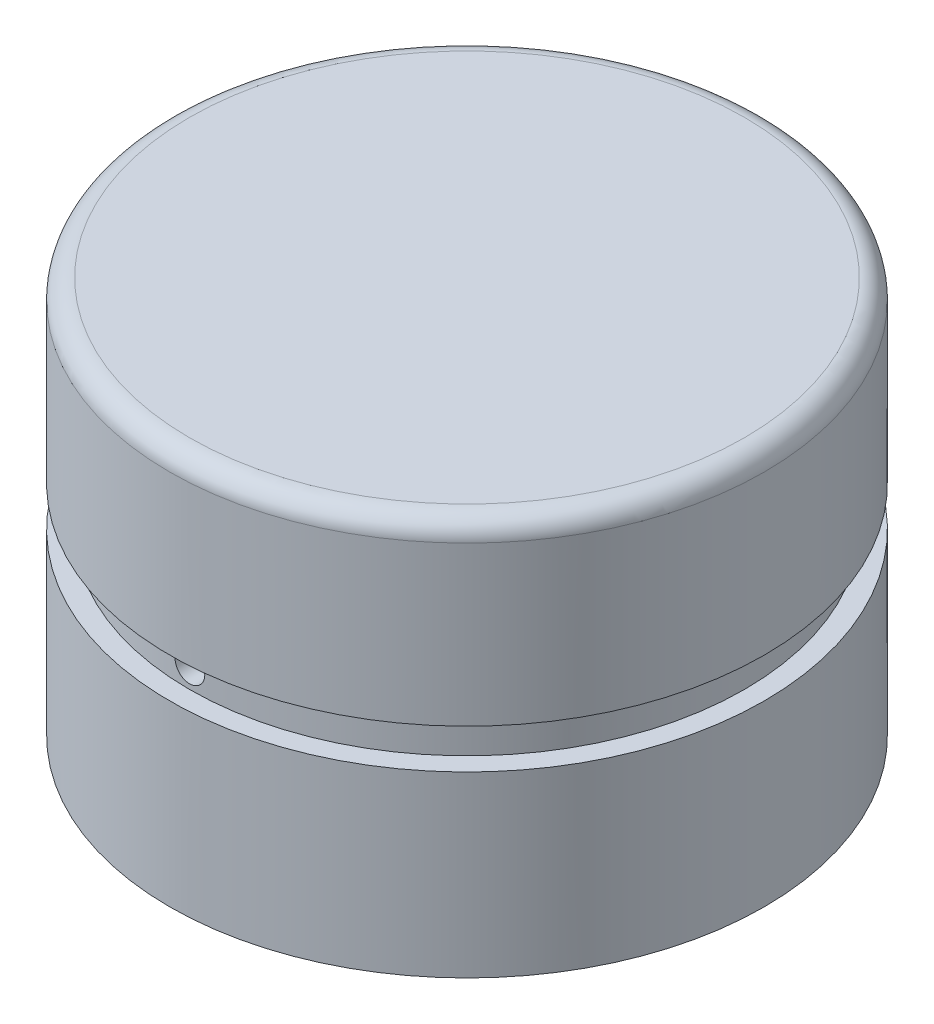
SolidWorks part; units mm, degrees
ref_plane "Front Plane" through (0, 0, 0) normal (0, 0, 1) x (1, 0, 0)
ref_plane "Top Plane" through (0, 0, 0) normal (0, 1, 0) x (1, 0, 0)
ref_plane "Right Plane" through (0, 0, 0) normal (1, 0, 0) x (0, 0, -1)
sketch "Sketch2" plane through (0, 0, 0) normal (0, 1, 0) x (1, 0, 0)
  circle A0 centre (0, 0) radius 7.5
  dimension "D1" = 15
extrude "Boss-Extrude1" add sketch "Sketch2" along normal mid plane 10 contours A0
sketch "Sketch3" plane through (0, -5, 0) normal (0, -1, 0) x (1, 0, 0)
  circle A0 centre (0, 0) radius 6.5
  circle A1 centre (0, 0) radius 7.5 construction
extrude "Cut-Extrude1" cut sketch "Sketch3" against normal offset from surface (9 mm away) 1 up to face at (0, 5, 7.5)
fillet "Fillet1" radius 0.5 1 edges at (0, 5, 7.5)
sketch "Sketch4" plane through (0, 4, 0) normal (0, -1, 0) x (1, 0, 0)
  circle A0 centre (0, 0) radius 2
  dimension "D1" = 4
extrude "Boss-Extrude2" add sketch "Sketch4" along normal blind 0.5
fillet "Fillet2" radius 0.1 1 edges at (0, 4, 2)
sketch "Sketch5" plane through (0, 0, 0) normal (0, 0, 1) x (1, 0, 0)
  line L0 (7.5, 0.5) -> (7, 0.5)
  line L1 (7.5, -5) -> (7.5, 4.5) construction
  line L2 (7, 0.5) -> (7, -0.5)
  line L3 (7, -0.5) -> (7.5, -0.5)
  line L4 (0, 0) -> (7.5, 0) construction
  line L5 (7.5, 0.5) -> (7.5, -0.5)
  line L6 (0, 0) -> (0, 5) construction
  line L7 (7, 5) -> (-7, 5) construction
  dimension "D1" = 0.5
  dimension "D2" = 1
revolve "Cut-Revolve1" cut sketch "Sketch5" angle 360 about L6
sketch "Sketch6" plane through (0, 0, 0) normal (0, 0, 1) x (1, 0, 0)
  circle A0 centre (0, 0) radius 0.375
  dimension "D1" = 0.75
extrude "Cut-Extrude2" cut sketch "Sketch6" against normal through all both and the other way through all
equation "\"Tappet Diameter\"= 15mm"
equation "\"Tappet Length\"= 20mm"
equation "\"D1@Sketch2\"=\"Tappet Diameter\""
equation "\"Wall Thickness\" = 1mm"
equation "\"D1@Sketch3\"=\"Wall Thickness\""
equation "\"D1@Cut-Extrude1\"=\"Wall Thickness\""
equation "\"D1@Sketch5\"=\"Wall Thickness\"/2"
